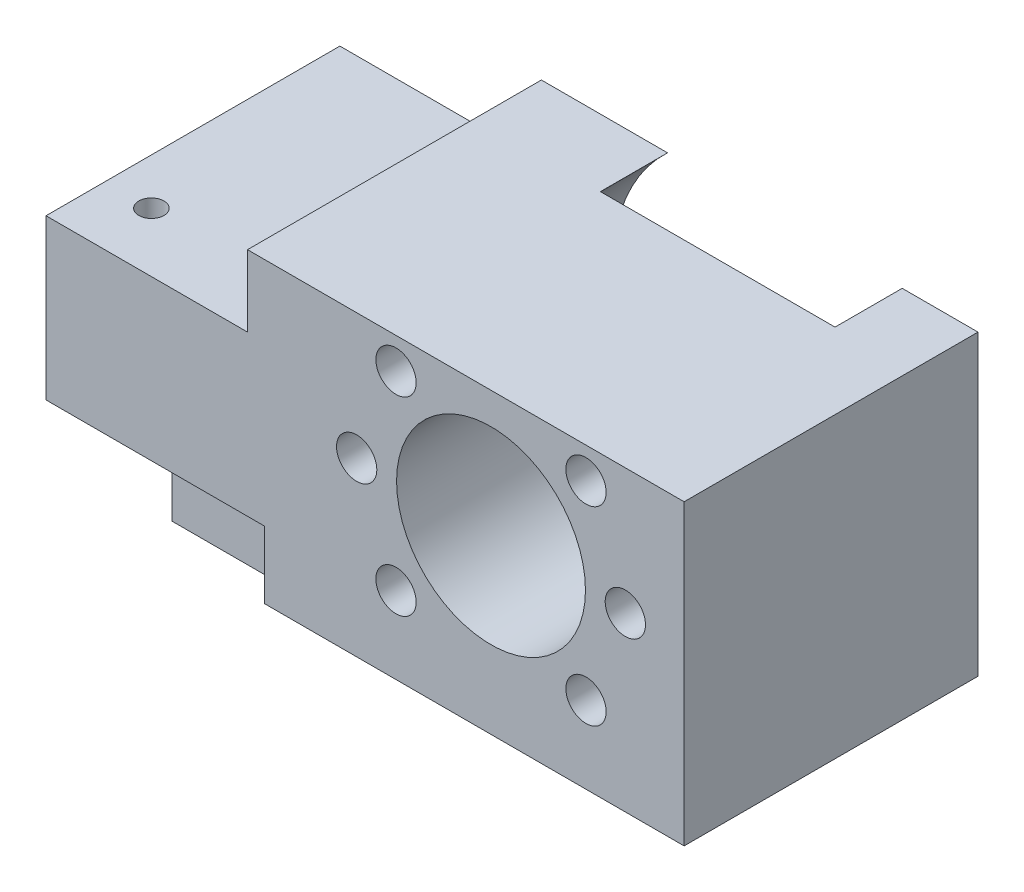
SolidWorks part; units mm, degrees
ref_plane "前视基准面" through (0, 0, 0) normal (0, 0, 1) x (1, 0, 0)
ref_plane "上视基准面" through (0, 0, 0) normal (0, 1, 0) x (1, 0, 0)
ref_plane "右视基准面" through (0, 0, 0) normal (1, 0, 0) x (0, 0, -1)
other "Configuration Table"
sketch "草图1" plane through (0, 0, 0) normal (0, 0, 1) x (1, 0, 0)
  line L1 (-35, -15) -> (35, -15)
  line L2 (-35, -15) -> (-35, 15)
  line L3 (-35, 15) -> (35, 15)
  line L4 (35, -15) -> (35, 15)
  line L5 (0, 15) -> (0, -15) construction
  line L6 (-35, 0) -> (35, 0) construction
  point P0 (0, 0)
  dimension "D1" = 70
  dimension "D2" = 30
extrude "凸台-拉伸1" add sketch "草图1" along normal blind 27
sketch "草图2" plane through (0, 0, 27) normal (0, 0, 1) x (1, 0, 0)
  line L0 (35, -15) -> (35, 15) construction
  line L1 (-35, 15) -> (-35, -15) construction
  line L2 (35, -15) -> (35, 15)
  line L3 (35, 15) -> (28.2288, 15)
  line L6 (-35, -15) -> (35, -15) construction
  line L7 (28.2288, -15) -> (35, -15)
  arc A0 (28.2288, -15) -> (28.2288, 15) centre (15, 0) ccw
  point P8 (-35, 0)
  line M6 (35, -15) -> (35, 15)
  line M7 (35, 15) -> (-35, 15)
  line M9 (-35, -15) -> (35, -15)
  dimension "D1" = 40
extrude "切除-拉伸1" cut sketch "草图2" against normal through all contours A0 M9 M6 | A0 L2 M7 region at (33.0451, -11.3888, 27) region at (33.0451, 11.3888, 27)
sketch "草图3" plane through (0, 0, 27) normal (0, 0, 1) x (1, 0, 0)
  line L0 (15, 0) -> (31, 0) construction
  line L1 (15, 0) -> (26.3137, 11.3137) construction
  line L2 (15, 0) -> (15, -16) construction
  circle A0 centre (31, 0) radius 2.4
  circle A1 centre (15, 0) radius 16 construction
  circle A2 centre (26.3137, 11.3137) radius 2.4
  circle A3 centre (26.3137, -11.3137) radius 2.4
  circle A4 centre (3.6863, 11.3137) radius 2.4
  circle A5 centre (3.6863, -11.3137) radius 2.4
  circle A6 centre (-1, 0) radius 2.4
  dimension "D1" = 32
  dimension "D3" = 4.8
  dimension "D2" = 45
extrude "切除-拉伸2" cut sketch "草图3" against normal through all
sketch "草图4" plane through (0, 0, 27) normal (0, 0, 1) x (1, 0, 0)
  line L1 (-35, 15) -> (-14, 15)
  line L2 (-35, 15) -> (-35, 6.5)
  line L3 (-35, 6.5) -> (-14, 6.5)
  line L4 (-14, 15) -> (-14, 6.5)
  dimension "D1" = 8.5
  dimension "D2" = 21
extrude "切除-拉伸3" cut sketch "草图4" against normal through all
sketch "草图7" plane through (0, 0, 0) normal (0, 0, -1) x (-1, 0, 0)
  circle A0 centre (-15, 0) radius 11.25
  dimension "D1" = 22.5
extrude "切除-拉伸5" cut sketch "草图7" against normal through all
sketch "草图8" plane through (0, 0, 0) normal (0, 0, -1) x (-1, 0, 0)
  line L0 (35, -15) -> (-28.2288, -15) construction
  line L1 (35, 6.5) -> (13.5, 6.5)
  line L2 (35, 6.5) -> (35, -15)
  line L3 (35, -15) -> (13.5, -15)
  line L4 (13.5, 6.5) -> (13.5, -15)
extrude "凸台-拉伸2" add sketch "草图8" along normal blind 8
sketch "草图10" plane through (0, -15, 0) normal (0, -1, 0) x (1, 0, 0)
  line L0 (-35, 27) -> (-35, -8) construction
  line L1 (-32.5, 3.95) -> (-17.5, 3.95) construction
  line L2 (-32.5, 3.95) -> (-32.5, 19.95) construction
  line L3 (-32.5, 19.95) -> (-17.5, 19.95) construction
  line L4 (-17.5, 3.95) -> (-17.5, 19.95) construction
  line L5 (-13.5, -8) -> (-35, -8) construction
  circle A0 centre (-32.5, 3.95) radius 1.5 construction
  circle A1 centre (-17.5, 3.95) radius 1.5 construction
  circle A2 centre (-17.5, 19.95) radius 1.5
  circle A3 centre (-32.5, 19.95) radius 1.5
  dimension "D5" = 3
  dimension "D1" = 2.5
  dimension "D2" = 11.95
  dimension "D3" = 16
  dimension "D4" = 15
extrude "切除-拉伸6" cut sketch "草图10" against normal through all
sketch "草图12" plane through (-35, 0, 0) normal (-1, 0, 0) x (0, 0, 1)
  line L4 (27, -15) -> (27, 6.5)
  line L5 (27, 6.5) -> (-8, 6.5)
  line L6 (-8, 6.5) -> (-8, -15)
  line L7 (-8, -15) -> (27, -15)
  line L8 (27, -15) -> (27, 6.5)
  line L9 (27, 6.5) -> (-8, 6.5)
  line L10 (-8, 6.5) -> (-8, -15)
  line L11 (-8, -15) -> (27, -15)
  dimension "D1" = 0
extrude "凸台-拉伸3" add sketch "草图12" along normal blind 3
sketch "草图13" plane through (0, -15, 0) normal (0, -1, 0) x (1, 0, 0)
  circle A1 centre (-32.5, 19.95) radius 3
  circle A2 centre (-17.5, 19.95) radius 3
  dimension "D1" = 6
extrude "切除-拉伸7" cut sketch "草图13" against normal blind 15
sketch "草图14" plane through (0, 0, 27) normal (0, 0, 1) x (1, 0, 0)
  line L1 (28.2288, -15) -> (35, -15)
  line L2 (28.2288, -15) -> (28.2288, -12.7603)
  line L4 (35, -15) -> (35, 0)
  line L5 (28.2288, -9.8671) -> (28.2288, 0)
  line L6 (28.2288, 9.8671) -> (28.2288, 0)
  line L7 (28.2288, 15) -> (35, 15)
  line L8 (28.2288, 15) -> (28.2288, 12.7603)
  line L10 (35, 15) -> (35, 0)
  arc A0 (28.2288, -15) -> (28.2288, 15) centre (15, 0) ccw construction
  circle A3 centre (26.3137, -11.3137) radius 2.4 construction
  arc A4 (28.2288, -12.7603) -> (28.2288, -9.8671) centre (26.3137, -11.3137) ccw
  circle A5 centre (26.3137, 11.3137) radius 2.4 construction
  arc A7 (28.2288, 9.8671) -> (28.2288, 12.7603) centre (26.3137, 11.3137) ccw
  circle A8 centre (31, 0) radius 2.4 construction
  circle A9 centre (31, 0) radius 2.4
extrude "凸台-拉伸4" add sketch "草图14" against normal blind 27
sketch "草图15" plane through (35, 0, 0) normal (1, 0, 0) x (0, 0, -1)
  line L4 (0, -15) -> (0, 15)
  line L5 (0, 15) -> (-27, 15)
  line L6 (-27, 15) -> (-27, -15)
  line L7 (-27, -15) -> (0, -15)
  line L8 (0, -15) -> (0, 15)
  line L9 (0, 15) -> (-27, 15)
  line L10 (-27, 15) -> (-27, -15)
  line L11 (-27, -15) -> (0, -15)
  dimension "D1" = 0
extrude "凸台-拉伸5" add sketch "草图15" along normal blind 3
sketch "草图16" plane through (0, -15, 0) normal (0, -1, 0) x (1, 0, 0)
  line L6 (-13.5, 0) -> (38, 0)
  line L7 (38, 0) -> (38, 27)
  line L8 (38, 27) -> (-38, 27)
  line L9 (-38, 27) -> (-38, -8)
  line L10 (-38, -8) -> (-13.5, -8)
  line L11 (-13.5, -8) -> (-13.5, 0)
  line L12 (-13.5, 0) -> (38, 0)
  line L13 (38, 0) -> (38, 27)
  line L14 (38, 27) -> (-38, 27)
  line L15 (-38, 27) -> (-38, -8)
  line L16 (-38, -8) -> (-13.5, -8)
  line L17 (-13.5, -8) -> (-13.5, 0)
  circle A1 centre (-32.5, 19.95) radius 3 construction
  circle A2 centre (-17.5, 19.95) radius 3 construction
  circle A5 centre (-32.5, 19.95) radius 3
  circle A6 centre (-17.5, 19.95) radius 3
  dimension "D1" = 0
extrude "凸台-拉伸6" add sketch "草图16" along normal blind 5.5
sketch "草图20" plane through (0, 0, 0) normal (0, 0, -1) x (-1, 0, 0)
  line L5 (14, 15) -> (-38, 15)
  line L6 (-38, 15) -> (-38, -20.5)
  line L7 (-38, -20.5) -> (13.5, -20.5)
  line L9 (14, 6.5) -> (14, 15)
  line L10 (14, 15) -> (-38, 15)
  line L11 (-38, 15) -> (-38, -20.5)
  line L14 (14, 6.5) -> (14, 15)
  line L16 (13.5, 6.5) -> (14, 6.5)
  line L17 (13.5, 6.5) -> (14, 6.5)
  line L18 (-38, -20.5) -> (13.5, -20.5)
  line L20 (13.5, -20.5) -> (13.5, 6.5)
  line L21 (13.5, -20.5) -> (13.5, 6.5)
  circle A0 centre (-15, 0) radius 11.25 construction
  circle A1 centre (-15, 0) radius 11.25
  dimension "D1" = 0
sketch "草图22" plane through (0, -20.5, 0) normal (0, -1, 0) x (1, 0, 0)
  line L1 (-38, 27) -> (-12, 27)
  line L2 (-38, 27) -> (-38, 12)
  line L3 (-38, 12) -> (-12, 12)
  line L4 (-12, 27) -> (-12, 12)
  dimension "D1" = 26
  dimension "D2" = 15
extrude "切除-拉伸9" cut sketch "草图22" against normal blind 8
extrude "凸台-拉伸8" add sketch "草图20" along normal blind 8
sketch "草图21" plane through (0, 0, -8) normal (0, 0, -1) x (-1, 0, 0)
  line L0 (-27.816, -16) -> (-2.184, -16)
  line L5 (14, 15) -> (-38, 15) construction
  arc A0 (-2.184, -16) -> (-27.816, -16) centre (-15, 0) ccw
  dimension "D1" = 41
  dimension "D2" = 31
extrude "切除-拉伸8" cut sketch "草图21" against normal blind 8
sketch "草图23" plane through (0, -20.5, 0) normal (0, -1, 0) x (1, 0, 0)
  line L0 (-38, -8) -> (38, -8) construction
  line L1 (-38, 12) -> (-12, 12)
  line L2 (-38, 12) -> (-38, -8)
  line L3 (-38, -8) -> (-12, -8)
  line L4 (-12, 12) -> (-12, -8)
  dimension "D1" = 26
extrude "凸台-拉伸9" add sketch "草图23" along normal blind 17
sketch "草图24" plane through (0, 0, -8) normal (0, 0, -1) x (-1, 0, 0)
  line L0 (12, -20.5) -> (-38, -20.5) construction
  line L2 (12, -37.5) -> (12, -20.5) construction
  circle A0 centre (17, -27) radius 2
  circle A1 centre (25, -27) radius 2
  dimension "D3" = 4
  dimension "D1" = 6.5
  dimension "D2" = 5
  dimension "D4" = 8
extrude "切除-拉伸10" cut sketch "草图24" against normal through all
sketch "草图25" plane through (0, 0, -8) normal (0, 0, -1) x (-1, 0, 0)
  circle A0 centre (17, -27) radius 3.75
  circle A1 centre (25, -27) radius 3.75
  dimension "D1" = 7.5
extrude "切除-拉伸11" cut sketch "草图25" against normal blind 5
sketch "草图26" plane through (0, -37.5, 0) normal (0, -1, 0) x (1, 0, 0)
  line L0 (-12, 12) -> (-38, 12) construction
  line L1 (-38, 12) -> (-38, -8) construction
  circle A0 centre (-31, 7) radius 3.1
  dimension "D1" = 6.2
  dimension "D2" = 5
  dimension "D3" = 7
extrude "切除-拉伸12" cut sketch "草图26" against normal blind 16
sketch "草图27" plane through (0, -21.5, 0) normal (0, -1, 0) x (1, 0, 0)
  circle A0 centre (-31, 7) radius 1.25
  dimension "D1" = 2.5
extrude "切除-拉伸13" cut sketch "草图27" against normal blind 10
sketch "草图28" plane through (0, -37.5, 0) normal (0, -1, 0) x (1, 0, 0)
  line L0 (-38, -8) -> (-12, -8) construction
  line L1 (-32, 4.0657) -> (-30, 4.0657)
  line L2 (-32, 4.0657) -> (-32, -8)
  line L3 (-32, -8) -> (-30, -8)
  line L4 (-30, 4.0657) -> (-30, -8)
  circle A0 centre (-31, 7) radius 3.1 construction
  dimension "D1" = 2
extrude "切除-拉伸14" cut sketch "草图28" against normal blind 16
fillet "圆角1" radius 2 2 edges at (-30, -29.5, 4.0657) (-32, -29.5, 4.0657)
sketch "草图29" plane through (-38, 0, 0) normal (-1, 0, 0) x (0, 0, 1)
  line L0 (-8, 6.5) -> (-8, -37.5) construction
  line L1 (12, -37.5) -> (-8, -37.5)
  line L2 (12, -37.5) -> (12, -32.5)
  line L3 (12, -32.5) -> (-8, -32.5)
  line L4 (-8, -37.5) -> (-8, -32.5)
  dimension "D1" = 5
extrude "切除-拉伸15" cut sketch "草图29" against normal through all
